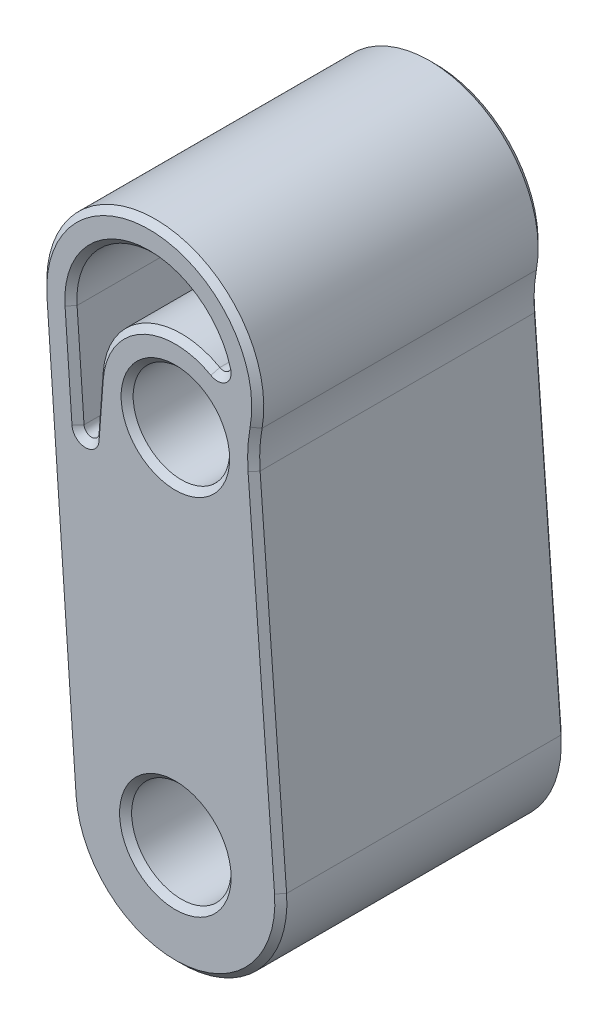
SolidWorks part; units mm, degrees
ref_plane "Front" through (0, 0, 0) normal (0, 0, 1) x (1, 0, 0)
ref_plane "Top" through (0, 0, 0) normal (0, 1, 0) x (1, 0, 0)
ref_plane "Right" through (0, 0, 0) normal (1, 0, 0) x (0, 0, -1)
sketch "Sketch1" plane through (0, 0, 0) normal (0, 0, 1) x (1, 0, 0)
  line L3 (-2.6, 0) -> (-1.6, 0) construction
  line L23 (1.65, -12) -> (2.65, -12) construction
  line L33 (-2.5927, 0.195) -> (-3.4901, -11.7375)
  line L34 (3.4901, -11.7375) -> (2.5927, 0.195)
  circle A0 centre (0, 0) radius 2.6 construction
  circle A3 centre (0, 0) radius 1.6
  circle A12 centre (0, -12) radius 1.65
  circle A13 centre (0, -12) radius 4.25 construction
  arc A22 (-2.5927, 0.195) -> (2.5927, 0.195) centre (0, 0) cw
  arc A28 (-3.4901, -11.7375) -> (3.4901, -11.7375) centre (0, -12) ccw
  dimension "D1" = 3.2
  dimension "D3" = 8.5
  dimension "D6" = 3.3
  dimension "D7" = 3.5
  dimension "D2" = 1
  dimension "D5" = 12
extrude "Boss-Extrude1" add sketch "Sketch1" along normal mid plane 9.5 contours A3 region at (0, -7.006, 0)
sketch "Sketch2" plane through (0, 0, 0) normal (0, 0, 1) x (1, 0, 0)
  line L0 (-3.4915, -12.2435) -> (-4.4576, 1.6074)
  line L1 (0, 0) -> (0, 8.0844) construction
  line L2 (0, 0) -> (-0.8664, 1.8579) construction
  line L3 (-0.8664, 1.8579) -> (-2.2187, 4.7581) construction
  line L4 (-2.2187, 4.7581) -> (-2.3878, 5.1206) construction
  arc A0 (-4.4576, 1.6074) -> (2.5206, 0.6378) centre (-0.8664, 1.8579) cw
  circle A1 centre (0, 0) radius 5.25 construction
  arc A2 (-3.4901, -11.7375) -> (3.4901, -11.7375) centre (0, -12) ccw construction
  arc A4 (2.5927, 0.195) -> (-2.5927, 0.195) centre (0, 0) ccw construction
  dimension "D2" = 10.5
  dimension "D4" = 3.6
  dimension "D1" = 0.4
  dimension "D3" = 25
extrude "Spring" add sketch "Sketch2" along normal through all and the other way through all thin thin type one direction wall 1
fillet "Spring Inside Fillets" radius 0.25 2 edges at (-2.9891, -5.0754, 0) (1.7324, 1.9388, 0)
fillet "Spring Outside Fillets" radius 5 1 edges at (2.5206, 0.6378, 0)
chamfer "Deburs" distance 0.2 angle 45 26 edges at (1.6, 0, -4.75) (1.65, -12, -4.75) (-1.3048, 4.4207, -4.75) (1.5529, 2.2861, -4.75) (-2.9804, -1.8672, -4.75) (-3.3446, 0.0212, -4.75) (0.253, -15.4908, -4.75) (3.0505, -5.8916, -4.75) (-1.2267, 2.2924, -4.75) (2.6034, 0.5883, -4.75) (-0.6702, 5.4526, -4.75) (-3.9746, -5.3181, -4.75) (1.65, -12, 4.75) (1.6, 0, 4.75) (1.5529, 2.2861, 4.75) (-1.3048, 4.4207, 4.75) (-3.3446, 0.0212, 4.75) (-2.9804, -1.8672, 4.75) (-0.6702, 5.4526, 4.75) (2.6034, 0.5883, 4.75) (-1.2267, 2.2924, 4.75) (3.0505, -5.8916, 4.75) (0.253, -15.4908, 4.75) (-3.9746, -5.3181, 4.75) (-2.6615, -0.7205, -4.75) (-2.6615, -0.7205, 4.75)
sketch "Sketch3" plane through (-4.3245, -0.3016, 0) normal (-0.9976, -0.0696, 0) x (0, 0, 1)
  line L1 (0, -0.5863) -> (0, -9.4709) construction
  line L6 (4.55, 1.9137) -> (-4.55, 1.9137) construction
  line L8 (4.55, -11.9709) -> (-4.55, -11.9709) construction
  dimension "D1" = 2.5
  dimension "D2" = 2.5
sketch "Sketch4" plane through (-4.3245, -0.3016, 0) normal (-0.9976, -0.0696, 0) x (0, 0, 1)
  line L0 (0, -0.5863) -> (0, -9.4709)
  line L1 (-2, -2.5863) -> (0, -0.5863)
  line L2 (0, -0.5863) -> (2, -2.5863)
  line L3 (0, -0.5863) -> (0, -9.4709) construction
  line L6 (0, -11.9519) -> (0, 0.0141) construction
  dimension "D1" = 45
  dimension "D2" = 2
extrude "Arrow Point" add sketch "Sketch4" along normal blind 0.2 draft 55 thin contours L1 | L2 thin type one direction wall 0.8
sketch "Sketch5" plane through (-4.3245, -0.3016, 0) normal (-0.9976, -0.0696, 0) x (0, 0, 1)
  line L0 (0, -0.9902) -> (0, -9.4709)
  line L1 (0, -0.5863) -> (0, -9.4709) construction
extrude "Arrow Shaft" add sketch "Sketch5" along normal blind 0.2 draft 55 thin thin type mid plane wall 0.8
equation "\"D1@Sketch1\"=\"Hardware Clearance Hole Diameter@Box Assy.Assembly\"+.05mm"
equation "\"D6@Sketch1\"=\"Hardware Clearance Hole Diameter@Box Assy.Assembly\"+.15mm"
